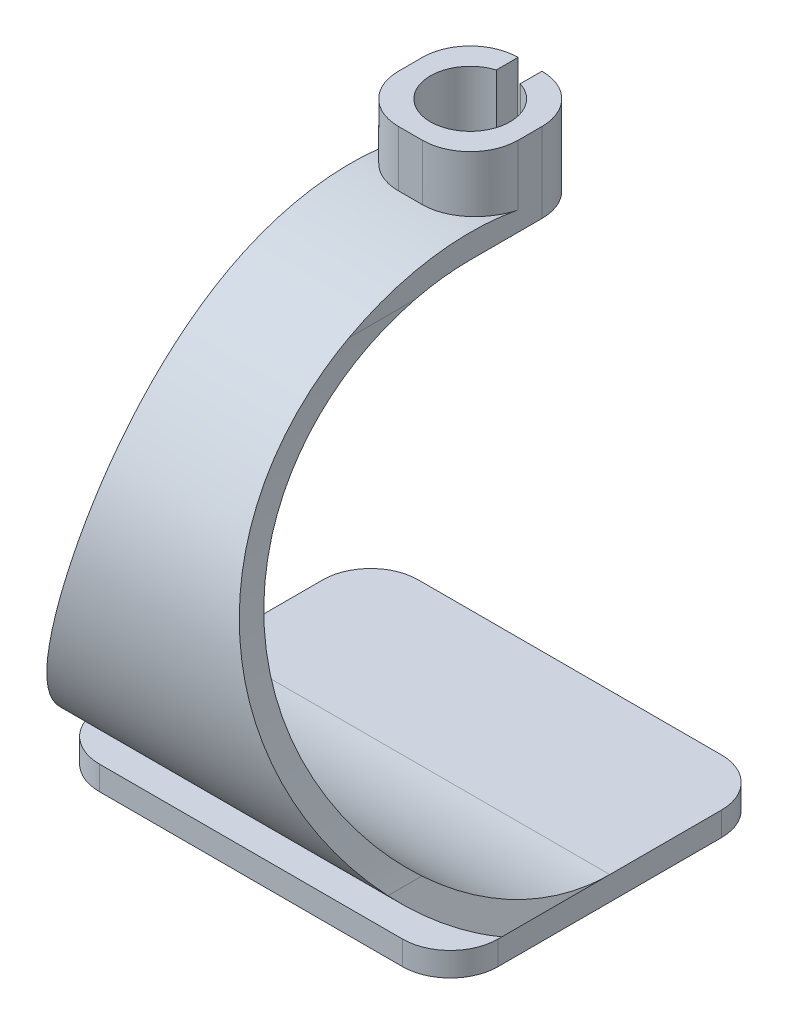
SolidWorks part; units mm, degrees
material "ABS"
ref_plane "Front Plane" through (0, 0, 0) normal (0, 0, 1) x (1, 0, 0)
ref_plane "Top Plane" through (0, 0, 0) normal (0, 1, 0) x (1, 0, 0)
ref_plane "Right Plane" through (0, 0, 0) normal (1, 0, 0) x (0, 0, -1)
sketch "Sketch2" plane through (0, 0, 0) normal (0, 1, 0) x (1, 0, 0)
  line L0 (-25, 0) -> (0, 0) construction
  line L1 (-25, 20) -> (25, 20)
  line L2 (-25, 20) -> (-25, -20)
  line L3 (-25, -20) -> (25, -20)
  line L4 (25, 20) -> (25, -20)
  line L5 (0, 0) -> (0, 20) construction
  dimension "D1" = 40
  dimension "D2" = 50
extrude "Boss-Extrude1" add sketch "Sketch2" along normal blind 3
sketch "Sketch3" plane through (-25, 0, 0) normal (-1, 0, 0) x (0, 0, 1)
  line L1 (0, 0) -> (0, 64) construction
  line L2 (0, 71) -> (0, 64)
  line L3 (0, 61) -> (-15, 61)
  line L4 (0, 3) -> (0, 0)
  line L5 (0, 71) -> (-15, 71)
  line L6 (-15, 61) -> (-15, 71)
  arc A0 (0, 0) -> (0, 64) centre (0, 32) ccw
  arc A1 (0, 3) -> (0, 61) centre (0, 32) ccw
  dimension "D2" = 32
  dimension "D1" = 64
  dimension "D4" = 10
  dimension "D5" = 15
  dimension "D3" = 3
extrude "Boss-Extrude2" add sketch "Sketch3" against normal blind 50
sketch "Sketch5" plane through (0, 0, 20) normal (0, 0, 1) x (1, 0, 0)
  line L0 (-25, 33.5) -> (25, 33.5) construction
  line L1 (-25, 64) -> (-25, 3) construction
  line L2 (25, 3) -> (25, 64) construction
  line L3 (-7.5, 71) -> (-7.5, 33.5)
  line L4 (25, 71) -> (-25, 71) construction
  line L5 (0, 33.5) -> (0, 71) construction
  line L6 (7.5, 71) -> (7.5, 33.5)
  line L7 (-7.5, 33.5) -> (-25, 3)
  line L8 (-25, 3) -> (-25, 71)
  line L9 (-25, 71) -> (-7.5, 71)
  line L10 (25, 71) -> (7.5, 71)
  line L11 (7.5, 33.5) -> (25, 3)
  line L12 (25, 3) -> (25, 71)
  dimension "D1" = 15
extrude "Cut-Extrude1" cut sketch "Sketch5" against normal blind 50 and the other way blind 50
fillet "Fillet1" radius 100 2 edges at (7.5, 33.5, 30.463) (-7.5, 33.5, 30.463)
fillet "Fillet3" radius 6 4 edges at (-7.5, 67.5, 0) (7.5, 67.5, 0) (7.5, 66, -15) (-7.5, 66, -15)
fillet "Fillet4" radius 6 4 edges at (-25, 1.5, -20) (25, 1.5, -20) (-25, 1.5, 20) (25, 1.5, 20)
sketch "Sketch6" plane through (0, 71, 0) normal (0, 1, 0) x (1, 0, 0)
  line L0 (0, 15) -> (0, 0) construction
  line L1 (1.5, 15) -> (-1.5, 15) construction
  line L2 (1.5, 0) -> (-1.5, 0) construction
  circle A0 centre (0, 7.5) radius 5
  dimension "D1" = 10
extrude "Cut-Extrude4" cut sketch "Sketch6" against normal blind 50
sketch "Sketch7" plane through (0, 0, -15) normal (0, 0, -1) x (-1, 0, 0)
  line L4 (1.5, 71) -> (-1.5, 71)
  line L5 (-1.5, 71) -> (-1.5, 61)
  line L6 (-1.5, 61) -> (1.5, 61)
  line L7 (1.5, 61) -> (1.5, 71)
  line L8 (1.5, 71) -> (-1.5, 71)
  line L9 (-1.5, 71) -> (-1.5, 61)
  line L10 (-1.5, 61) -> (1.5, 61)
  line L11 (1.5, 61) -> (1.5, 71)
  dimension "D1" = 0
extrude "Cut-Extrude5" cut sketch "Sketch7" against normal blind 10
